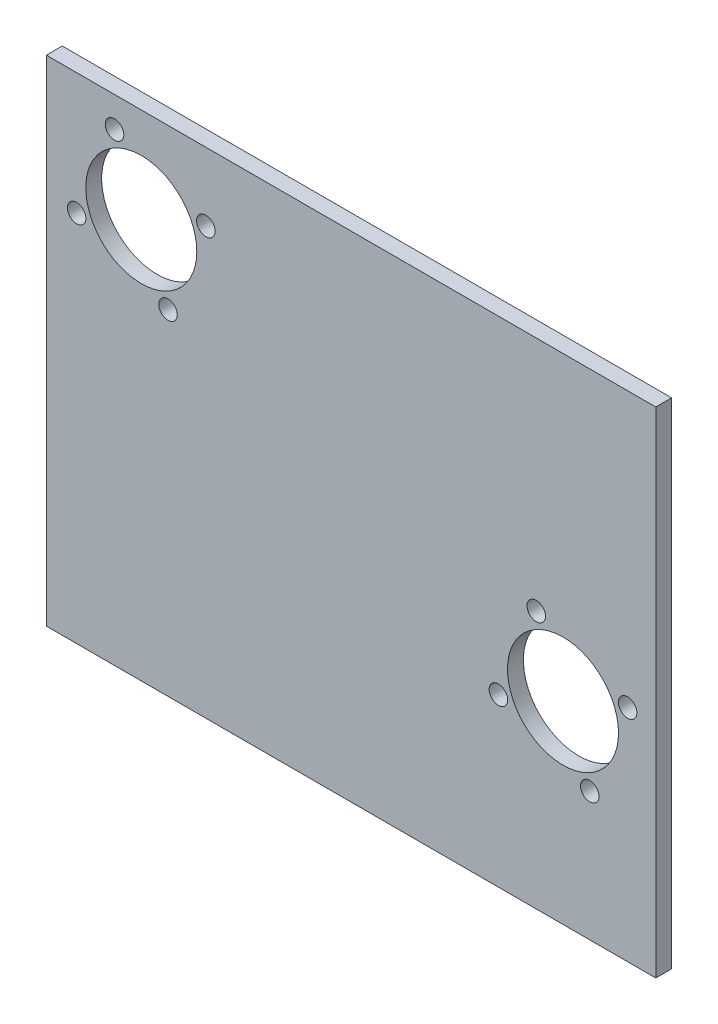
SolidWorks part; units mm, degrees
material "6061-T6 (SS)"
ref_plane "Front" through (0, 0, 0) normal (0, 0, 1) x (1, 0, 0)
ref_plane "Top" through (0, 0, 0) normal (0, 1, 0) x (1, 0, 0)
ref_plane "Right" through (0, 0, 0) normal (1, 0, 0) x (0, 0, -1)
ref_axis "side-side" through (80.9, 0, 0) along (-1, 0, 0)
ref_axis "up-down" through (0, 50, 0) along (0, -1, 0)
ref_axis "front-back" through (0, 0, -80.9) along (0, 0, 1)
sketch "Sketch1" plane through (0, 0, 0) normal (0, 0, 1) x (1, 0, 0)
  line L3 (-19, 19) -> (103, 19)
  line L4 (-19, -80) -> (-19, 19)
  line L5 (103, 19) -> (103, -80)
  line L6 (-19, -80) -> (103, -80)
  line L8 (0, 0) -> (-5.3524, 12.9364) construction
  line L9 (84.4311, -41.275) -> (79.0787, -28.3386) construction
  line L10 (84.4311, -41.275) -> (71.4947, -46.6274) construction
  circle A1 centre (0, 0) radius 11.1125
  circle A2 centre (-5.3524, 12.9364) radius 1.8542
  circle A3 centre (-12.9364, -5.3524) radius 1.8542
  circle A4 centre (12.9364, 5.3524) radius 1.8542
  circle A5 centre (5.3524, -12.9364) radius 1.8542
  circle A6 centre (84.4311, -41.275) radius 11.1125
  circle A8 centre (79.0787, -28.3386) radius 1.8542
  circle A9 centre (71.4947, -46.6274) radius 1.8542
  circle A10 centre (89.7836, -54.2114) radius 1.8542
  circle A11 centre (97.3676, -35.9226) radius 1.8542
  point P5 (0, 0)
  point P8 (0, 0)
  point P28 (0, 0)
  dimension "D1" = 22.225
  dimension "D2" = 3.7084
  dimension "D4" = 38.725
  dimension "D5" = 80
  dimension "D6" = 18.5689
  dimension "D7" = 103
  dimension "D8" = 19
  dimension "D3" = 19
extrude "Boss-Extrude1" add sketch "Sketch1" against normal blind 3.175
